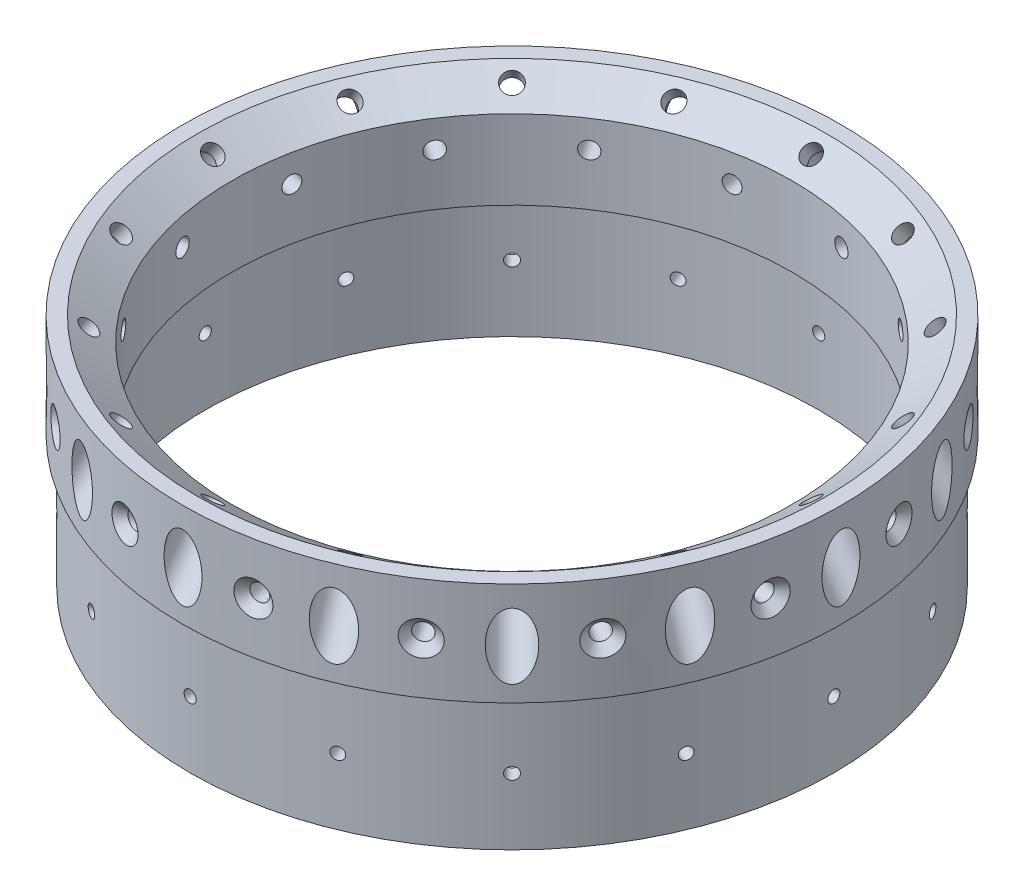
SolidWorks part; units mm, degrees
material "6063-T6"
ref_plane "Front Plane" through (0, 0, 0) normal (0, 0, 1) x (1, 0, 0)
ref_plane "Top Plane" through (0, 0, 0) normal (0, 1, 0) x (1, 0, 0)
ref_plane "Right Plane" through (0, 0, 0) normal (1, 0, 0) x (0, 0, -1)
sketch "Main sketch" plane through (0, 0, 0) normal (0, 0, 1) x (1, 0, 0)
  line L0 (0, 0) -> (-87, 0) construction
  line L8 (-85, -35) -> (-81, -35)
  line L23 (-87, 0) -> (-87, 27.1992)
  line L24 (-83, 27.1992) -> (-74, 20.8973)
  line L25 (-74, 20.8973) -> (-74, 0)
  line L26 (-74, 0) -> (-81, 0)
  line L27 (-81, 0) -> (-81, -35)
  line L28 (-87, 0) -> (-85, 0)
  line L29 (-85, 0) -> (-85, -35)
  line L30 (0, 0) -> (0, -35.5238) construction
  line L31 (-87, 27.1992) -> (-83, 27.1992)
  line L32 (-74, 20.8973) -> (-87, 20.8973) construction
  point P4 (-87, 30)
  dimension "D1" = 87
  dimension "D2" = 2
  dimension "D3" = 4
  dimension "D4" = 55
  dimension "D5" = 30
  dimension "D6" = 13
  dimension "D7" = 35
  dimension "D8" = 4
  dimension "D9" = 90
revolve "Main revolve" add sketch "Main sketch" angle 360 about L30
sketch "Hole position" plane through (0, 0, 0) normal (0, 0, 1) x (1, 0, 0)
  line L0 (-79, 24.3983) -> (-83, 18.6857) construction
  line L1 (-83, 27.1992) -> (-74, 20.8973) construction
  line L2 (0, 30) -> (0, -2.3509) construction
  line L4 (-83, 27.1992) -> (-83, -10.9444) construction
  line L6 (87, 30) -> (-87, 30) construction
  line L7 (-83, 18.6857) -> (-67.2656, 7.6684) construction
  point P7 (-79, 24.3983)
  dimension "D1" = 4
ref_plane "Hole plane" through (-18.5267, -26.4589, 0) normal (-0.5736, -0.8192, 0) x (0.8192, -0.5736, 0)
sketch "Sketch14" plane through (-18.5267, -26.4589, 0) normal (-0.5736, -0.8192, 0) x (0.8192, -0.5736, 0)
  circle A1 centre (-78.7073, 0) radius 5
  dimension "D1" = 5
extrude "Hole extrude 1" cut sketch "Sketch14" against normal blind 3 and the other way through all
hole_wizard "screw extrude" positions "3DSketch13" profile "Sketch15" hole size "Ø5.0" standard "DIN" end condition up to next
sketch3d "3DSketch13"
  line L0 (-79, 24.3983, 0) -> (-83, 18.6857, 0) construction
  point P0 (-81.2793, 21.1432, 0)
sketch "Sketch15" plane through (-81.2793, 21.1432, 0) normal (0, 0, 1) x (0.8192, -0.5736, 0)
  line L0 (0, 0) -> (0, 3.9738)
  line L1 (0, 3.9738) -> (2.5, 3.9738)
  line L2 (2.5, 3.9738) -> (2.5, 0)
  line L5 (2.5, 0) -> (0, 0)
  line L11 (0, -9.7231) -> (0, 107.95) construction
  spline S0 degree 2 poles (-5, -2.833) (0, -9.4728) (5, -17.1145) knots 0 0 0 1 1 1 weights 0.082 0.087 0.092 construction
  dimension "Thru Hole Dia." = 5
  dimension "Thru Hole Depth" = 3.9738
pattern_circular "Screw holes pattern" count 16 over 360 about axis through (0, 0, 0) along (0, 1, 0) of "Hole extrude 1", "screw extrude" reverse direction yes
ref_plane "Płaszczyzna1" through (16.9729, 0, 85.3283) normal (0.1951, 0, 0.9808) x (0, 1, 0)
ref_plane "Plane1" through (0, 0, 85) normal (0, 0, 1) x (1, 0, 0)
sketch "Sketch16" plane through (0, 0, 85) normal (0, 0, 1) x (1, 0, 0)
  line L1 (-85, -35) -> (85, -35) construction
  circle A0 centre (0, -17.5) radius 1.6
  point P0 (0, -17.5)
  dimension "D2" = 3.2
  dimension "D1" = 17.5
extrude "Cut-Extrude1" cut sketch "Sketch16" against normal up to next
pattern_circular "CirPattern1" count 16 over 360 about axis through (0, -35, 0) along (0, 1, 0) of "Cut-Extrude1"
ref_plane "Plane2" through (0, 13.5996, 0) normal (0, 1, 0) x (1, 0, 0)
sketch "Sketch17" plane through (0, 13.5996, 0) normal (0, 1, 0) x (1, 0, 0)
  line L0 (-67.9079, -13.5077) -> (-85.3283, -16.9729)
  line L1 (0, 0) -> (-67.9079, -13.5077)
  line L2 (-85.3283, -16.9729) -> (-86.2062, -12.5593)
  line L3 (-67.9079, -13.5077) -> (-68.3449, -11.3108)
  line L4 (-86.2062, -12.5593) -> (-84.4498, -13.733)
  line L5 (-68.3449, -11.3108) -> (-85.7673, -14.7661)
  line L6 (-84.4498, -13.733) -> (-83.559, -14.3281)
  arc A0 (-92.5258, 0) -> (-90.7479, -18.0509) centre (0, 0) ccw construction
  circle A1 centre (0, 0) radius 87 construction
  arc A2 (-85.7941, -14.6312) -> (-84.4498, -13.733) centre (-86.2062, -12.5593) ccw construction
revolve "Cut-Revolve1" cut sketch "Sketch17" angle 360 about L0 region at (-76.8435, 13.5996, 14.1406) region at (-85.1775, 13.5996, 13.8845)
pattern_circular "CirPattern2" count 16 over 360 about axis through (0, 0, 0) along (0, 1, 0) of "Cut-Revolve1" reverse direction yes
